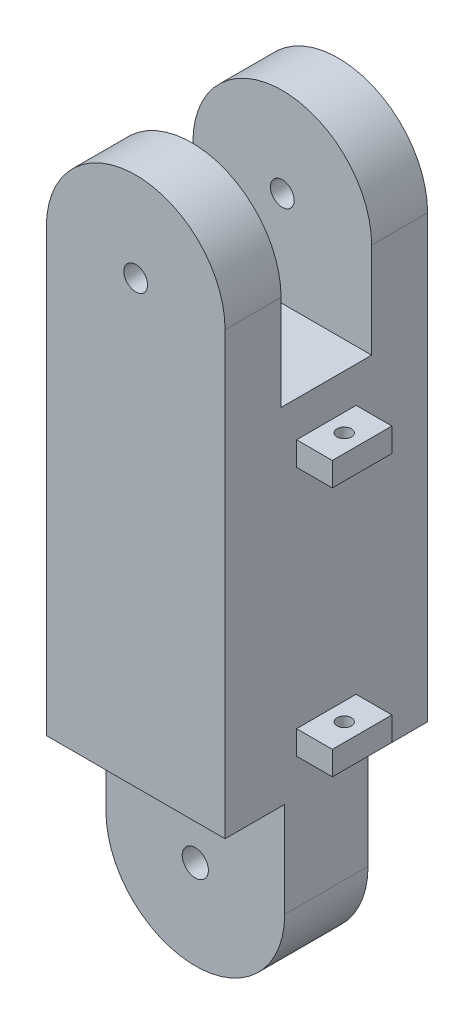
SolidWorks part; units mm, degrees
ref_plane "Front Plane" through (0, 0, 0) normal (0, 0, 1) x (1, 0, 0)
ref_plane "Top Plane" through (0, 0, 0) normal (0, 1, 0) x (1, 0, 0)
ref_plane "Right Plane" through (0, 0, 0) normal (1, 0, 0) x (0, 0, -1)
sketch "Finger_Skeleton" plane through (0, 0, 0) normal (0, 0, -1) x (-1, 0, 0)
  line L0 (0, 0) -> (0, 45)
  line L1 (0, 45) -> (0, 70)
  line L2 (0, 70) -> (0, 93)
  circle A1 centre (0, 0) radius 5 construction
  circle A2 centre (0, 45) radius 5 construction
  circle A3 centre (0, 70) radius 5 construction
  dimension "D4" = 10
  dimension "D5" = 10
  dimension "D6" = 10
  dimension "D1" = 45
  dimension "D2" = 25
  dimension "D3" = 23
sketch "Link1_Outline" plane through (0, 0, 0) normal (0, 0, 1) x (1, 0, 0)
  line L0 (0, 0) -> (0, 45) construction
  line L1 (-7.5, 0) -> (-7.5, 45)
  line L2 (7.5, 0) -> (7.5, 45)
  arc A0 (-7.5, 0) -> (7.5, 0) centre (0, 0) ccw
  arc A1 (7.5, 45) -> (-7.5, 45) centre (0, 45) ccw
  point P4 (0, 22.5)
  dimension "D1" = 15
extrude "Link1_Body" add sketch "Link1_Outline" along normal mid plane 17
sketch "Sketch1" plane through (7.5, 0, 0) normal (1, 0, 0) x (0, 0, -1)
  line L0 (0, 0) -> (0, 45) construction
  line L1 (3.5, -8) -> (9, -8)
  line L2 (3.5, -8) -> (3.5, 7.9981)
  line L3 (3.5, 7.9981) -> (9, 7.9981)
  line L4 (9, -8) -> (9, 7.9981)
  line L5 (-8.5, -7.5) -> (8.5, -7.5) construction
  line L6 (0, 8.25) -> (0, -8.25) construction
  line L7 (-9, -8) -> (-9, 7.9981)
  line L8 (-3.5, 7.9981) -> (-9, 7.9981)
  line L9 (-3.5, -8) -> (-3.5, 7.9981)
  line L10 (-3.5, -8) -> (-9, -8)
  dimension "D1" = 3.5
  dimension "D2" = 5.5
  dimension "D3" = 15.9981
  dimension "D4" = 0.5
extrude "Tongue_Cut" cut sketch "Sketch1" against normal through all both and the other way through all
sketch "Sketch2" plane through (0, 0, 0) normal (1, 0, 0) x (0, 0, -1)
  line L0 (0, 0) -> (0, 45) construction
  line L1 (3.8, 37) -> (-3.8, 37)
  line L2 (3.8, 37) -> (3.8, 55)
  line L3 (3.8, 55) -> (-3.8, 55)
  line L4 (-3.8, 37) -> (-3.8, 55)
  dimension "D1" = 3.8
  dimension "D2" = 18
  dimension "D3" = 7.6
  dimension "D4" = 37
extrude "Slot_Cut" cut sketch "Sketch2" against normal through all both and the other way through all
sketch "Sketch3" plane through (0, 0, 0) normal (0, 0, 1) x (1, 0, 0)
  circle A0 centre (0, 0) radius 1.1
  circle A1 centre (0, 45) radius 1
  dimension "D1" = 2.2
  dimension "D2" = 2
extrude "Pin_Holes" cut sketch "Sketch3" against normal through all both and the other way through all
sketch "Sketch4" plane through (0, 0, 0) normal (0, 0, 1) x (1, 0, 0)
  line L0 (0, 0) -> (0, 45) construction
  line L1 (7, 13) -> (10.5, 13)
  line L2 (7, 13) -> (7, 11)
  line L3 (7, 11) -> (10.5, 11)
  line L4 (10.5, 13) -> (10.5, 11)
  dimension "D1" = 7
  dimension "D2" = 3.5
  dimension "D3" = 11
  dimension "D4" = 2
extrude "Guide_Block_1" add sketch "Sketch4" along normal mid plane 5
sketch "Sketch5" plane through (0, 0, 0) normal (0, 0, 1) x (1, 0, 0)
  line L0 (0, 0) -> (0, 45) construction
  line L1 (7.0006, 32) -> (10.5006, 32)
  line L2 (7.0006, 32) -> (7.0006, 34)
  line L3 (7.0006, 34) -> (10.5006, 34)
  line L4 (10.5006, 32) -> (10.5006, 34)
  dimension "D1" = 7.0006
  dimension "D2" = 32
  dimension "D3" = 3.5
  dimension "D4" = 2
extrude "Guide_Block_2" add sketch "Sketch5" along normal mid plane 5
sketch "Sketch6" plane through (0, 0, 0) normal (0, 1, 0) x (1, 0, 0)
  line L0 (10.5006, -2.5) -> (7.5, -2.5) construction
  circle A0 centre (9, 0) radius 0.6
  dimension "D1" = 1.2
  dimension "D2" = 9
  dimension "D3" = 2.5
extrude "Cord_Guides" cut sketch "Sketch6" along normal through all both and the other way through all
